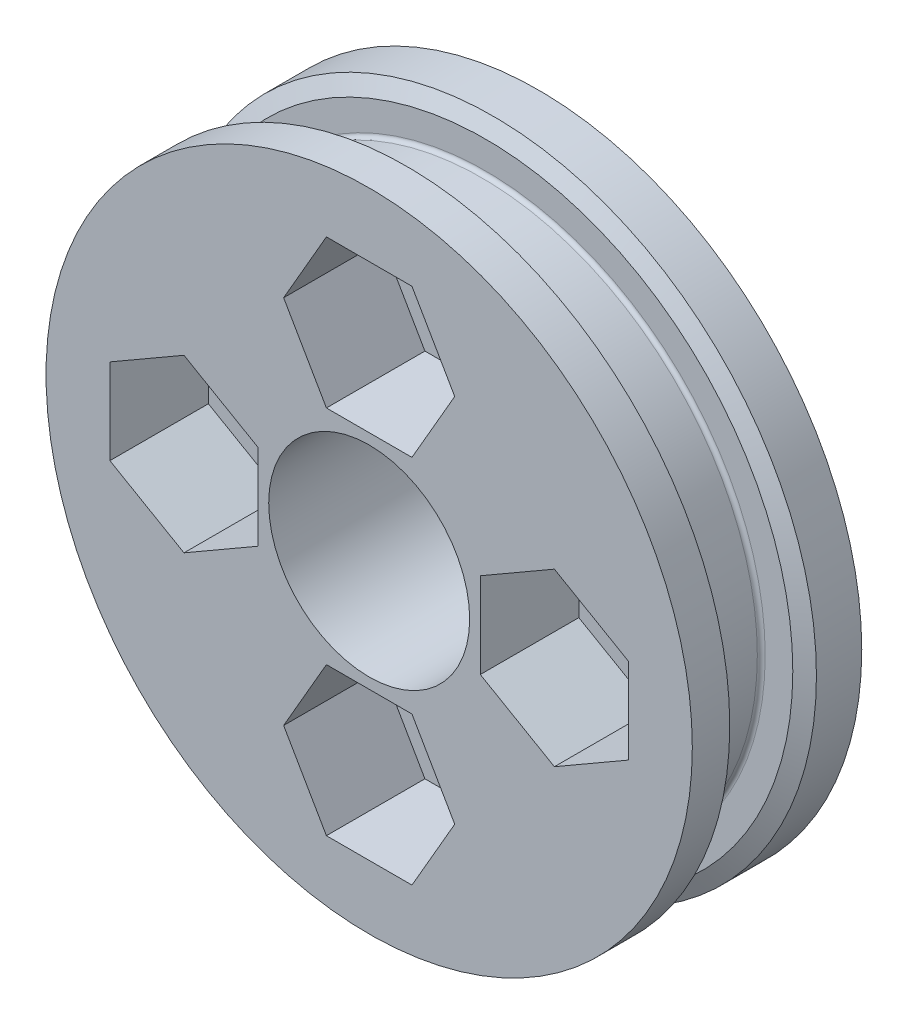
SolidWorks part; units mm, degrees
ref_plane "Front Plane" through (0, 0, 0) normal (0, 0, 1) x (1, 0, 0)
ref_plane "Top Plane" through (0, 0, 0) normal (0, 1, 0) x (1, 0, 0)
ref_plane "Right Plane" through (0, 0, 0) normal (1, 0, 0) x (0, 0, -1)
sketch "Sketch2" plane through (0, 0, 0) normal (1, 0, 0) x (0, 0, -1)
  line L0 (0, 6.477) -> (0, 20.828)
  line L1 (0, 20.828) -> (2.413, 20.828)
  line L2 (2.921, 19.812) -> (2.921, 17.78)
  line L3 (2.921, 17.78) -> (7.493, 17.78)
  line L4 (7.493, 17.78) -> (7.493, 19.812)
  line L5 (8.001, 20.828) -> (10.922, 20.828)
  line L6 (10.922, 20.828) -> (10.922, 6.477)
  line L8 (0, 6.477) -> (10.922, 6.477)
  line L9 (0, 6.477) -> (0, 0) construction
  line L10 (0, 0) -> (10.7816, 0) construction
  line L11 (7.493, 19.812) -> (8.001, 20.828)
  line L12 (2.413, 20.828) -> (2.921, 19.812)
  point P4 (2.921, 20.828)
  point P7 (7.493, 20.828)
  dimension "D1" = 17.78
  dimension "D2" = 10.922
  dimension "D3" = 3.048
  dimension "D4" = 6.477
  dimension "D5" = 4.572
  dimension "D6" = 1.016
  dimension "D7" = 0.508
  dimension "D8" = 0.508
  dimension "D9" = 1.016
  dimension "D10" = 2.921
revolve "Revolve1" add sketch "Sketch2" angle 360 about L10
sketch "Sketch3" plane through (0, 0, -10.922) normal (0, 0, -1) x (-1, 0, 0)
  line L1 (-8.255, -8.255) -> (8.255, -8.255)
  line L2 (-8.255, -8.255) -> (-8.255, 8.255)
  line L3 (-8.255, 8.255) -> (8.255, 8.255)
  line L4 (8.255, -8.255) -> (8.255, 8.255)
  circle A0 centre (0, 0) radius 6.477 construction
  circle A1 centre (0, 0) radius 6.477
  point P4 (8.255, 0)
  point P6 (0, 8.255)
  dimension "D1" = 16.51
extrude "Boss-Extrude1" add sketch "Sketch3" along normal blind 3.175
ref_plane "Plane1" through (0, 0, -5.461) normal (0, 0, -1) x (-1, 0, 0)
sketch "Sketch4" plane through (0, 0, -10.922) normal (0, 0, -1) x (-1, 0, 0)
  line L0 (0, 11.938) -> (0, 0) construction
  line L1 (0, 0) -> (0, -11.938) construction
  line L2 (-11.938, 0) -> (0, 0) construction
  line L3 (0, 0) -> (11.938, 0) construction
  circle A0 centre (0, 11.938) radius 2.54
  circle A1 centre (11.938, 0) radius 2.54
  circle A2 centre (0, -11.938) radius 2.54
  circle A3 centre (-11.938, 0) radius 2.54
  dimension "D1" = 5.08
  dimension "D2" = 11.938
extrude "Cut-Extrude1" cut sketch "Sketch4" against normal through all both and the other way through all
fillet "Fillet1" radius 0.254 2 edges at (17.78, 0, -7.493) (17.78, 0, -2.921)
sketch "Sketch5" plane through (0, 0, 0) normal (0, 0, 1) x (1, 0, 0)
  line L1 (2.757, 7.1628) -> (5.5139, 11.938)
  line L2 (5.5139, 11.938) -> (2.757, 16.7132)
  line L3 (2.757, 16.7132) -> (-2.757, 16.7132)
  line L4 (-2.757, 16.7132) -> (-5.5139, 11.938)
  line L5 (-5.5139, 11.938) -> (-2.757, 7.1628)
  line L6 (-2.757, 7.1628) -> (2.757, 7.1628)
  circle A0 centre (0, 11.938) radius 4.7752 construction
  circle A1 centre (0, 11.938) radius 2.54 construction
  dimension "D1" = 9.5504
extrude "Cut-Extrude2" cut sketch "Sketch5" against normal blind 6.35
pattern_circular "CirPattern1" count 4 over 360 about axis through (0, 0, 0) along (0, 0, 1) of "Cut-Extrude2"
